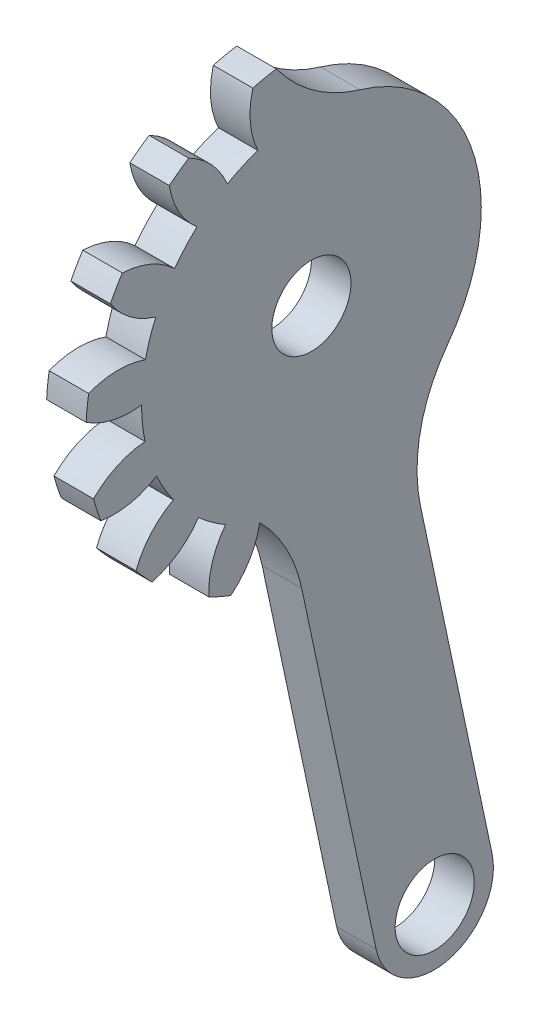
SolidWorks part; units mm, degrees
ref_plane "Front Plane" through (0, 0, 0) normal (0, 0, 1) x (1, 0, 0)
ref_plane "Top Plane" through (0, 0, 0) normal (0, 1, 0) x (1, 0, 0)
ref_plane "Right Plane" through (0, 0, 0) normal (1, 0, 0) x (0, 0, -1)
ref_plane "Plane1" through (-1.3549, 0, 0) normal (1, 0, 0) x (0, 0, -1)
sketch "Sketch1" plane through (-1.3549, 0, 0) normal (1, 0, 0) x (0, 0, -1)
  circle A0 centre (0, 0) radius 1.5
  arc A1 (-11.6614, 0.7808) -> (-8.5926, -0.0513) centre (-9.1308, 4.0384) ccw
  arc A2 (-8.5926, -0.0513) -> (-8.4155, -1.7363) centre (0, 0) ccw
  arc A3 (-8.4155, -1.7363) -> (-11.2442, -3.1883) centre (-8.0917, -5.8486) ccw
  arc A4 (-11.2442, -3.1883) -> (-10.9708, -4.0298) centre (0, 0) ccw
  arc A5 (-10.9708, -4.0298) -> (-7.8289, -3.5418) centre (-9.984, -0.0246) ccw
  arc A6 (-7.8289, -3.5418) -> (-6.9817, -5.0091) centre (0, 0) ccw
  arc A7 (-6.9817, -5.0091) -> (-8.9753, -7.4861) centre (-5.0133, -8.6341) ccw
  arc A8 (-8.9753, -7.4861) -> (-8.3833, -8.1436) centre (0, 0) ccw
  arc A9 (-8.3833, -8.1436) -> (-5.7114, -6.4199) centre (-9.1108, -4.0833) ccw
  arc A10 (-5.7114, -6.4199) -> (-4.3407, -7.4157) centre (0, 0) ccw
  arc A11 (-4.3407, -7.4157) -> (-5.1545, -10.4895) centre (-1.068, -9.9267) ccw
  arc A12 (-5.1545, -10.4895) -> (-4.3462, -10.8493) centre (0, 0) ccw
  arc A13 (-4.3462, -10.8493) -> (-2.6064, -8.1879) centre (-6.6623, -7.436) ccw
  arc A14 (-2.6064, -8.1879) -> (-0.9492, -8.5402) centre (0, 0) ccw
  arc A15 (-0.9492, -8.5402) -> (-0.4424, -11.6791) centre (3.0619, -9.5029) ccw
  arc A16 (-0.4424, -11.6791) -> (0.4424, -11.6791) centre (0, 0) ccw
  arc A17 (0.4424, -11.6791) -> (0.9492, -8.5402) centre (-3.0619, -9.5029) ccw
  arc A18 (0.9492, -8.5402) -> (2.6064, -8.1879) centre (0, 0) ccw
  arc A19 (2.6064, -8.1879) -> (4.3462, -10.8493) centre (6.6623, -7.436) ccw
  arc A20 (4.3462, -10.8493) -> (5.1545, -10.4895) centre (0, 0) ccw
  arc A21 (5.1545, -10.4895) -> (4.3407, -7.4157) centre (1.068, -9.9267) ccw
  arc A22 (4.3407, -7.4157) -> (5.7114, -6.4199) centre (0, 0) ccw
  arc A23 (5.7114, -6.4199) -> (8.3833, -8.1436) centre (9.1108, -4.0833) ccw
  arc A24 (8.3833, -8.1436) -> (8.9753, -7.4861) centre (0, 0) ccw
  arc A25 (8.9753, -7.4861) -> (6.9817, -5.0091) centre (5.0133, -8.6341) ccw
  arc A26 (6.9817, -5.0091) -> (7.8289, -3.5418) centre (0, 0) ccw
  arc A27 (7.8289, -3.5418) -> (10.9708, -4.0298) centre (9.984, -0.0246) ccw
  arc A28 (10.9708, -4.0298) -> (11.2442, -3.1883) centre (0, 0) ccw
  arc A29 (11.2442, -3.1883) -> (8.4155, -1.7363) centre (8.0917, -5.8486) ccw
  arc A30 (8.4155, -1.7363) -> (8.5926, -0.0513) centre (0, 0) ccw
  arc A31 (8.5926, -0.0513) -> (11.6614, 0.7808) centre (9.1308, 4.0384) ccw
  arc A32 (11.6614, 0.7808) -> (11.5689, 1.6608) centre (0, 0) ccw
  arc A33 (11.5689, 1.6608) -> (8.3942, 1.8367) centre (9.7709, -2.0518) ccw
  arc A34 (8.3942, 1.8367) -> (7.8706, 3.448) centre (0, 0) ccw
  arc A35 (7.8706, 3.448) -> (10.3356, 5.4564) centre (6.6989, 7.4031) ccw
  arc A36 (10.3356, 5.4564) -> (9.8932, 6.2227) centre (0, 0) ccw
  arc A37 (9.8932, 6.2227) -> (6.9214, 5.0921) centre (9.7607, 2.0998) ccw
  arc A38 (6.9214, 5.0921) -> (5.7877, 6.3512) centre (0, 0) ccw
  arc A39 (5.7877, 6.3512) -> (7.2227, 9.1886) centre (3.1086, 9.4877) ccw
  arc A40 (7.2227, 9.1886) -> (6.5069, 9.7086) centre (0, 0) ccw
  arc A41 (6.5069, 9.7086) -> (4.2519, 7.4671) centre (8.0628, 5.8883) ccw
  arc A42 (4.2519, 7.4671) -> (2.7041, 8.1562) centre (0, 0) ccw
  arc A43 (2.7041, 8.1562) -> (2.861, 11.3319) centre (-1.0192, 9.9319) ccw
  arc A44 (2.861, 11.3319) -> (1.9955, 11.5159) centre (0, 0) ccw
  arc A45 (1.9955, 11.5159) -> (0.8471, 8.5509) centre (4.9707, 8.6587) ccw
  arc A46 (0.8471, 8.5509) -> (-0.8471, 8.5509) centre (0, 0) ccw
  arc A47 (-0.8471, 8.5509) -> (-1.9955, 11.5159) centre (-4.9707, 8.6587) ccw
  arc A48 (-1.9955, 11.5159) -> (-2.861, 11.3319) centre (0, 0) ccw
  arc A49 (-2.861, 11.3319) -> (-2.7041, 8.1562) centre (1.0192, 9.9319) ccw
  arc A50 (-2.7041, 8.1562) -> (-4.2519, 7.4671) centre (0, 0) ccw
  arc A51 (-4.2519, 7.4671) -> (-6.5069, 9.7086) centre (-8.0628, 5.8883) ccw
  arc A52 (-6.5069, 9.7086) -> (-7.2227, 9.1886) centre (0, 0) ccw
  arc A53 (-7.2227, 9.1886) -> (-5.7877, 6.3512) centre (-3.1086, 9.4877) ccw
  arc A54 (-5.7877, 6.3512) -> (-6.9214, 5.0921) centre (0, 0) ccw
  arc A55 (-6.9214, 5.0921) -> (-9.8932, 6.2227) centre (-9.7607, 2.0998) ccw
  arc A56 (-9.8932, 6.2227) -> (-10.3356, 5.4564) centre (0, 0) ccw
  arc A57 (-10.3356, 5.4564) -> (-7.8706, 3.448) centre (-6.6989, 7.4031) ccw
  arc A58 (-7.8706, 3.448) -> (-8.3942, 1.8367) centre (0, 0) ccw
  arc A59 (-8.3942, 1.8367) -> (-11.5689, 1.6608) centre (-9.7709, -2.0518) ccw
  arc A60 (-11.5689, 1.6608) -> (-11.6614, 0.7808) centre (0, 0) ccw
extrude "Boss-Extrude1" add sketch "Sketch1" against normal blind 2
sketch "Sketch3" plane through (-1.3549, 0, 0) normal (1, 0, 0) x (0, 0, -1)
  line L0 (30.2794, 0) -> (-60.3175, 0) construction
  circle A0 centre (0, 0) radius 11.4072
  circle A1 centre (-20, 0) radius 11.4072 construction
  arc A2 (-8.5926, -0.0513) -> (-8.4155, -1.7363) centre (0, 0) ccw construction
  dimension "D1" = 20
extrude "Cut-Extrude1" cut sketch "Sketch3" against normal through all flip side to cut
sketch "Sketch4" plane through (-3.3549, 0, 0) normal (-1, 0, 0) x (0, 0, 1)
  circle A0 centre (0, 0) radius 2
  dimension "D1" = 4
extrude "Cut-Extrude2" cut sketch "Sketch4" against normal through all
sketch "Sketch5" plane through (-1.3549, 0, 0) normal (1, 0, 0) x (0, 0, -1)
  line L0 (0, 0) -> (13.4318, -63.1917)
  line L1 (-2.1713, -4.2139) -> (3.2716, -29.8211)
  line L4 (-2.1713, -4.2139) -> (3.9627, -4.2139)
  line L5 (0, 0) -> (0, 37.2709) construction
  line L6 (3.9627, -4.2139) -> (9.1405, -28.5736)
  circle A1 centre (6.2374, -29.3444) radius 2
  circle A2 centre (0, 0) radius 30 construction
  arc A3 (3.2716, -29.8211) -> (9.1405, -28.5736) centre (6.2061, -29.1973) ccw
  dimension "D3" = 4
  dimension "D1" = 60
  dimension "D2" = 3
  dimension "D4" = 192
  dimension "D5" = 3
extrude "Boss-Extrude3" add sketch "Sketch5" against normal blind 2 contours L1 A3 L0 A1 L4 | L0 A3 L6 L4 A1 region at (-1.3549, -16.7734, -5.1257) region at (-1.3549, -17.0961, -2.0617)
sketch "Sketch6" plane through (-1.3549, 0, 0) normal (1, 0, 0) x (0, 0, -1)
  line L1 (-0.6372, -11.4316) -> (-1.2603, -8.4998)
  line L2 (-1.8788, -8.3848) -> (-2.5034, -11.1723)
  line L3 (-2.5034, -11.1723) -> (-1.8788, -8.3848)
  line L4 (0, 8.5928) -> (0, 11.4494)
  line L5 (4.6086, -7.2523) -> (4.8064, -8.183) construction
  line L6 (4.6086, -7.2523) -> (5.2317, -10.1841)
  line L7 (-0.6765, -11.2466) -> (3.2716, -29.8211) construction
  arc A0 (-2.5034, -11.1723) -> (-0.6372, -11.4316) centre (0, 0) ccw
  arc A1 (-1.8788, -8.3848) -> (-1.2603, -8.4998) centre (0, 0) ccw
  arc A2 (5.2317, -10.1841) -> (0, 11.4494) centre (0, 0) ccw
  arc A3 (4.6086, -7.2523) -> (0, 8.5928) centre (0, 0) ccw
extrude "Cut-Extrude3" cut sketch "Sketch6" against normal through all contours A3 L6 A2 L4 | A1 L2 A0 L1 region at (-1.3549, -10.1287, 1.5716) region at (-1.3549, 10.0211, -0.2448)
fillet "Fillet1" radius 8 3 edges at (-2.3549, -8.4998, 1.2603) (-2.3549, -7.2523, -4.6086) (-2.3549, 8.5509, 0.8471)
